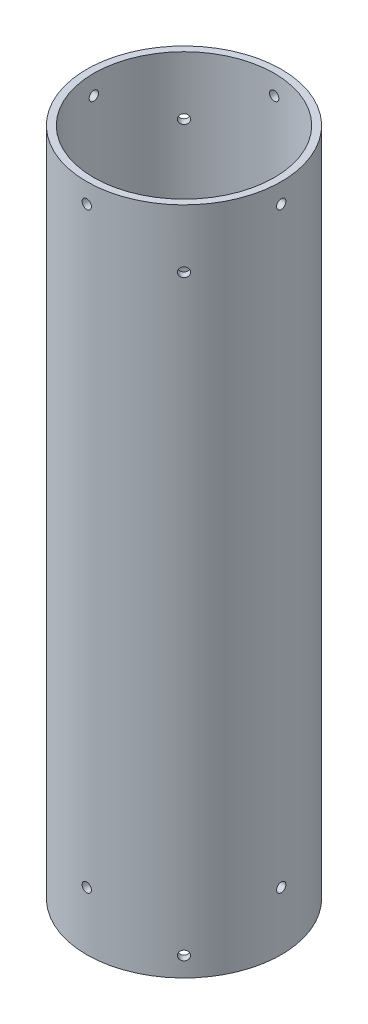
SolidWorks part; units mm, degrees
material "ПВХ 0.007 Смягченный"
ref_plane "Спереди" through (0, 0, 0) normal (0, 0, 1) x (1, 0, 0)
ref_plane "Сверху" through (0, 0, 0) normal (0, 1, 0) x (1, 0, 0)
ref_plane "Справа" through (0, 0, 0) normal (1, 0, 0) x (0, 0, -1)
sketch "Эскиз1" plane through (0, 0, 0) normal (0, 1, 0) x (1, 0, 0)
  circle A0 centre (0, 0) radius 25
  circle A1 centre (0, 0) radius 23.2
  dimension "ExDBody" = 50
  dimension "InDBody" = 46.4
extrude "Бобышка-Вытянуть1" add sketch "Эскиз1" along normal blind 172
ref_plane "Плоскость1" through (0, 31, 0) normal (0, -1, 0) x (-1, 0, 0)
sketch "Эскиз3" plane through (0, 0, 0) normal (1, 0, 0) x (0, 0, -1)
  line L0 (23.2, 172) -> (-23.2, 172) construction
  line L2 (-25, 0) -> (25, 0) construction
  circle A0 centre (0, 167) radius 1.2
  circle A3 centre (0, 15) radius 1.2
  dimension "D1" = 5
  dimension "D3" = 15
  dimension "D2" = 2.4
  dimension "D4" = 2.4
extrude "Вырез-Вытянуть2" cut sketch "Эскиз3" against normal through all
pattern_circular "Круговой массив1" count 4 over 360 about axis through (0, 172, 0) along (0, -1, 0) of "Вырез-Вытянуть2"
ref_plane "Плоскость2" through (0, 0, 0) normal (-0.7071, 0, 0.7071) x (0, -1, 0)
sketch "Эскиз11" plane through (0, 0, 0) normal (-0.7071, 0, 0.7071) x (0, -1, 0)
  line L0 (-172, 0) -> (0, 0) construction
  line L1 (0, -25) -> (0, 25) construction
  line L2 (-172, 25) -> (-172, -25) construction
  circle A0 centre (-5, 0) radius 1.2
  circle A1 centre (-157, 0) radius 1.2
  dimension "D1" = 2.4
  dimension "D3" = 15
  dimension "D4" = 2.4
  dimension "D2" = 5
extrude "Вырез-Вытянуть10" cut sketch "Эскиз11" against normal through all
pattern_circular "Круговой массив2" count 4 over 360 about axis through (0, 172, 0) along (0, -1, 0) of "Вырез-Вытянуть10"
sketch "Эскиз13" plane through (0, 0, 0) normal (-0.7071, 0, 0.7071) x (0, -1, 0)
  text T0 "Fire Way\r\n\r\n Spark" font "Blazed" height in points 40
  point P1 (0, 0)
